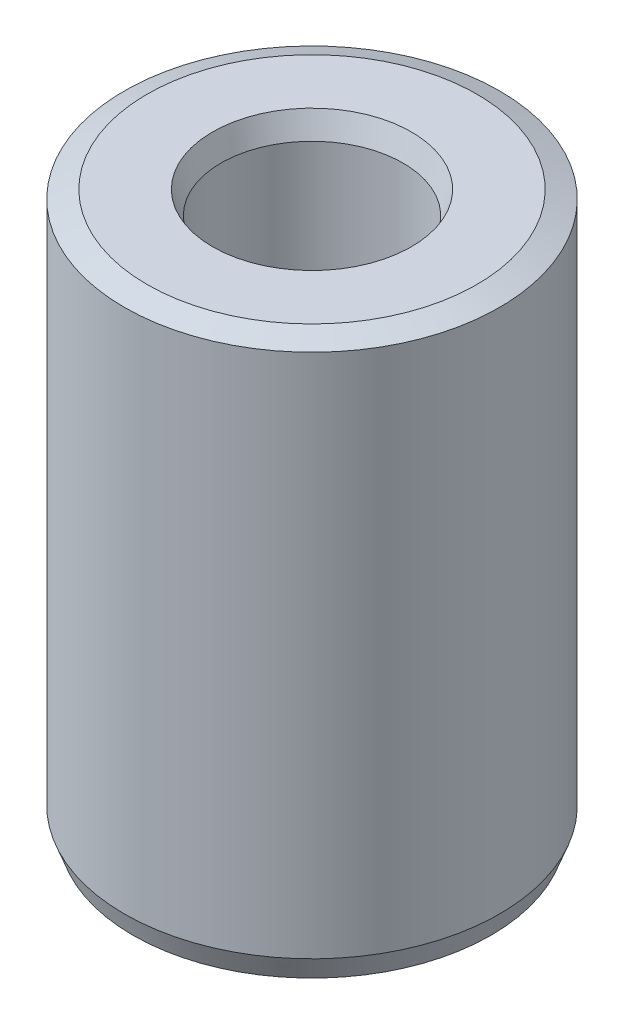
SolidWorks part; units mm, degrees
ref_plane "Front Plane" through (0, 0, 0) normal (0, 0, 1) x (1, 0, 0)
ref_plane "Top Plane" through (0, 0, 0) normal (0, 1, 0) x (1, 0, 0)
ref_plane "Right Plane" through (0, 0, 0) normal (1, 0, 0) x (0, 0, -1)
sketch "Sketch1" plane through (0, 0, 0) normal (0, 1, 0) x (1, 0, 0)
  circle A0 centre (0, 0) radius 50
  dimension "SLEEVE_OD" = 100
extrude "Boss-Extrude1" add sketch "Sketch1" along normal blind 148.3342
sketch "Sketch2" plane through (0, 0, 0) normal (0, 1, 0) x (1, 0, 0)
  circle A0 centre (0, 0) radius 24.2578
  dimension "BORE_D" = 48.5155
extrude "Cut-Extrude1" cut sketch "Sketch2" along normal through all
chamfer "Chamfer1" distance 2.2572 angle 69.526 4 edges at (0, 148.3342, 24.2578) (0, 0, 24.2578) (0, 0, 50) (0, 148.3342, 50) first distance on face at (0, 148.3342, 24.2578) first distance on face at (0, 0, 24.2578) first distance on face at (0, 148.3342, 50)
